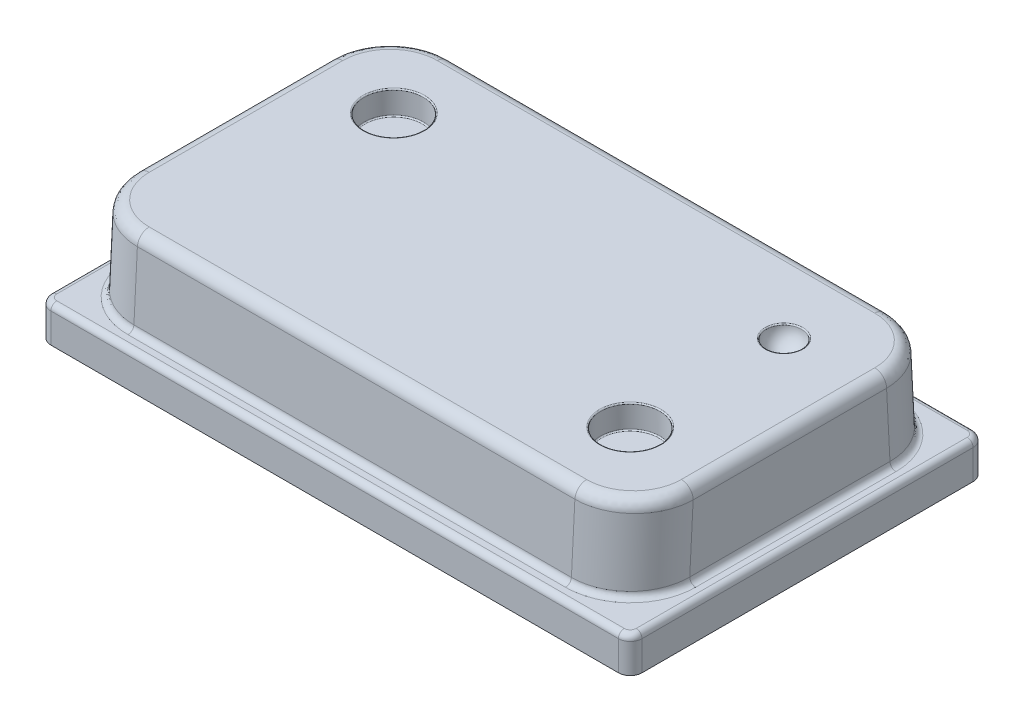
SolidWorks part; units mm, degrees
ref_plane "Ön Düzlem" through (0, 0, 0) normal (0, 0, 1) x (1, 0, 0)
ref_plane "Üst Düzlem" through (0, 0, 0) normal (0, 1, 0) x (1, 0, 0)
ref_plane "Sağ Düzlem" through (0, 0, 0) normal (1, 0, 0) x (0, 0, -1)
sketch "Çizim1" plane through (0, 0, 0) normal (0, 1, 0) x (1, 0, 0)
  line L1 (-2.5, -1.5) -> (2.5, -1.5)
  line L2 (-2.5, -1.5) -> (-2.5, 1.5)
  line L3 (-2.5, 1.5) -> (2.5, 1.5)
  line L4 (2.5, -1.5) -> (2.5, 1.5)
  line L5 (-2.5, -1.5) -> (2.5, 1.5) construction
  line L6 (-2.5, 1.5) -> (2.5, -1.5) construction
  point P0 (0, 0)
  dimension "D1" = 3
  dimension "D2" = 5
extrude "Yükseklik-Ekstrüzyon1" add sketch "Çizim1" along normal blind 0.3
sketch "Çizim3" plane through (0, 0, 0) normal (1, 0, 0) x (0, 0, -1)
  line L0 (-1.35, 0.3) -> (1.35, 0.3)
  line L1 (-1.5, 0.3) -> (1.5, 0.3) construction
  line L2 (-1.35, 0.3) -> (-1.3133, 1)
  line L3 (-1.3133, 1) -> (1.3133, 1)
  line L4 (1.3133, 1) -> (1.35, 0.3)
  line L5 (-1.5, 0) -> (1.5, 0) construction
  point P3 (0, 0.3)
  dimension "D1" = 2.7
  dimension "D2" = 87
  dimension "D3" = 87
  dimension "D4" = 1
extrude "Yükseklik-Ekstrüzyon3" add sketch "Çizim3" along normal mid plane 4.7
sketch "Çizim5" plane through (0, 1, 0) normal (0, 1, 0) x (1, 0, 0)
  line L0 (2.35, 0) -> (-2.35, 0) construction
  line L1 (2.35, 1.3133) -> (2.35, -1.3133) construction
  line L2 (-2.35, 1.3133) -> (-2.35, -1.3133) construction
  circle A0 centre (1.65, -0.65) radius 0.25
  circle A1 centre (-1.65, 0.65) radius 0.25
  dimension "D5" = 0.5
  dimension "D1" = 1.65
  dimension "D2" = 1.65
  dimension "D3" = 0.65
  dimension "D4" = 0.65
extrude "Kes-Ekstrüzyon1" cut sketch "Çizim5" against normal blind 0.2
sketch "Çizim11" plane through (0, 1, 0) normal (0, 1, 0) x (1, 0, 0)
  line L0 (1.65, -0.65) -> (1.65, 0.65) construction
  circle A0 centre (1.65, 0.65) radius 0.15
  dimension "D2" = 0.3
  dimension "D1" = 0.65
extrude "Kes-Ekstrüzyon3" cut sketch "Çizim11" against normal blind 0.15 contours A0
fillet "Radyus13" radius 0.15 1 edges at (1.65, 0.85, -0.5)
fillet "Radyus6" radius 0.1 4 edges at (2.5, 0.15, 1.5) (-2.5, 0.15, 1.5) (2.5, 0.15, -1.5) (-2.5, 0.15, -1.5)
fillet "Radyus8" radius 0.5 4 edges at (-2.35, 0.65, 1.3317) (-2.35, 0.65, -1.3317) (2.35, 0.65, 1.3317) (2.35, 0.65, -1.3317)
fillet "Radyus9" radius 0.1 8 edges at (0, 1, 1.3133) (-2.2036, 1, 1.1667) (-2.35, 1, 0) (-2.2036, 1, -1.1667) (0, 1, -1.3133) (2.2036, 1, -1.1667) (2.35, 1, 0) (2.2036, 1, 1.1667)
fillet "Radyus10" radius 0.05 8 edges at (2.4707, 0.3, -1.4707) (2.5, 0.3, 0) (2.4707, 0.3, 1.4707) (0, 0.3, 1.5) (-2.4707, 0.3, 1.4707) (-2.5, 0.3, 0) (-2.4707, 0.3, -1.4707) (0, 0.3, -1.5)
fillet "Radyus11" radius 0.05 8 edges at (2.2036, 0.3, 1.2034) (2.35, 0.3, 0) (2.2036, 0.3, -1.2034) (0, 0.3, -1.35) (-2.2036, 0.3, -1.2034) (-2.35, 0.3, 0) (-2.2036, 0.3, 1.2034) (0, 0.3, 1.35)
fillet "Radyus12" radius 0.01 4 edges at (1.65, 0.8, 0.9) (1.65, 1, 0.9) (-1.65, 0.8, -0.4) (-1.65, 1, -0.4)
fillet "Radyus14" radius 0.01 1 edges at (1.65, 1, -0.5)
